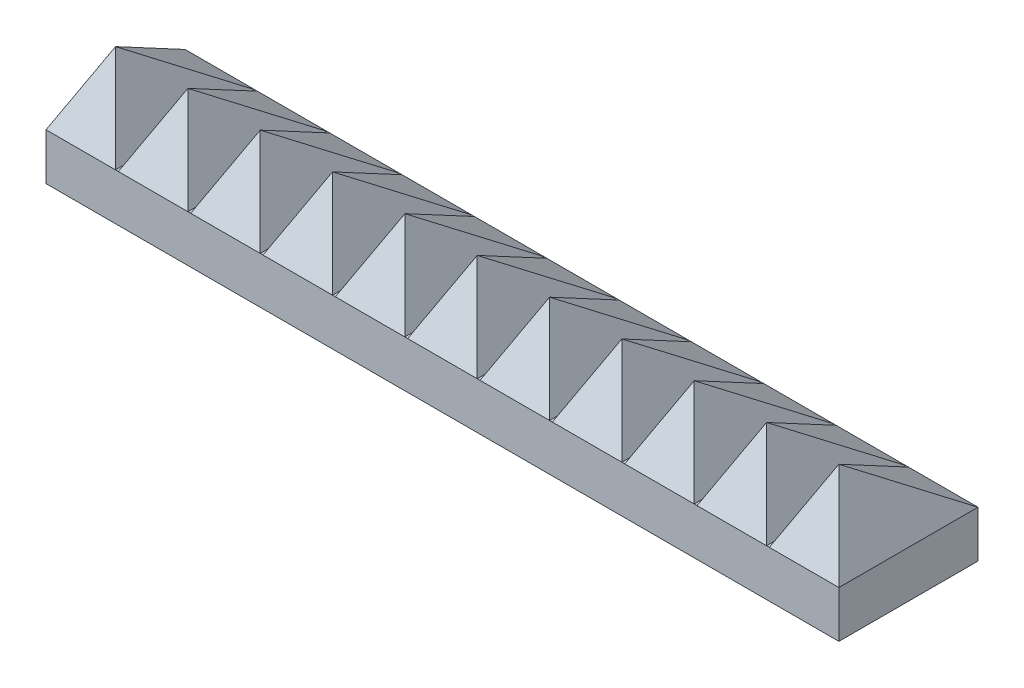
SolidWorks part; units mm, degrees
ref_plane "Front Plane" through (0, 0, 0) normal (0, 0, 1) x (1, 0, 0)
ref_plane "Top Plane" through (0, 0, 0) normal (0, 1, 0) x (1, 0, 0)
ref_plane "Right Plane" through (0, 0, 0) normal (1, 0, 0) x (0, 0, -1)
sketch "Sketch1" plane through (0, 0, 0) normal (0, 1, 0) x (1, 0, 0)
  line L1 (0, 0) -> (19.05, 0)
  line L2 (0, 0) -> (0, -19.05)
  line L3 (0, -19.05) -> (19.05, -19.05)
  line L4 (19.05, 0) -> (19.05, -19.05)
extrude "Boss-Extrude2" add sketch "Sketch1" along normal blind 6.35
ref_plane "Plane2" through (0, 26.0731, 0) normal (0, 1, 0) x (1, 0, 0)
sketch "Sketch8" plane through (0, 0, 0) normal (0, 1, 0) x (1, 0, 0)
  line L9 (0, 9.525) -> (217.17, 9.525)
  line L10 (0, 9.525) -> (0, -28.575)
  line L11 (0, -28.575) -> (217.17, -28.575)
  line L12 (217.17, 9.525) -> (217.17, -28.575)
extrude "Boss-Extrude4" add sketch "Sketch8" along normal blind 6.35 contours L11 L12 L9 L10
extrude "Boss-Extrude5" add sketch "Sketch8<5>" against normal blind 6.4262 contours L11 L12 L9 L10
sketch "Sketch8<5>" plane through (0, 0, 0) normal (0, 1, 0) x (1, 0, 0) same geometry as "Sketch8"
sketch "Sketch9" plane through (0, 6.35, 0) normal (0, 1, 0) x (1, 0, 0)
  line L0 (0, -28.575) -> (217.17, -28.575) construction
  line L1 (0, 9.525) -> (19.05, 9.525)
  line L2 (0, 9.525) -> (0, -28.575)
  line L3 (0, -28.575) -> (19.05, -28.575)
  line L4 (19.05, 9.525) -> (19.05, -28.575)
sketch "Sketch13" plane through (0, 6.35, 0) normal (0, 1, 0) x (1, 0, 0)
  line L0 (0, -9.525) -> (19.05, -28.575)
  line L1 (0, 9.525) -> (0, -28.575) construction
  line L2 (19.05, -28.575) -> (19.05, -9.525)
  line L3 (19.05, 9.525) -> (19.05, -28.575) construction
  line L4 (19.05, -9.525) -> (0, -28.575)
ref_plane "Plane4" through (0, 26.0731, 0) normal (0, 1, 0) x (1, 0, 0)
sketch "Sketch14" plane through (0, 26.0731, 0) normal (0, 1, 0) x (1, 0, 0)
  line L0 (0, -9.525) -> (19.05, -28.575) construction
  point P0 (9.525, -19.05)
loft "Loft3" add profiles "Sketch9", "Sketch14"
pattern_linear "LPattern3" count 11 spacing 19.812 along (1, 0, 0) of "Loft3"
sketch "Sketch15" plane through (0, -6.4262, 0) normal (0, -1, 0) x (1, 0, 0)
  line L0 (217.17, -9.525) -> (217.17, 28.575) construction
  line L1 (0, -9.525) -> (0, 28.575) construction
  circle A0 centre (179.07, 9.525) radius 12.192
  circle A1 centre (38.1, 9.525) radius 12.192
  circle A2 centre (108.585, 9.525) radius 12.192
  dimension "D1" = 38.1
  dimension "D2" = 70.485
  dimension "D3" = 38.1
  dimension "D4" = 24.384
  dimension "D5" = 24.384
  dimension "D6" = 24.384
extrude "Boss-Extrude6" add sketch "Sketch15" along normal blind 6.35
